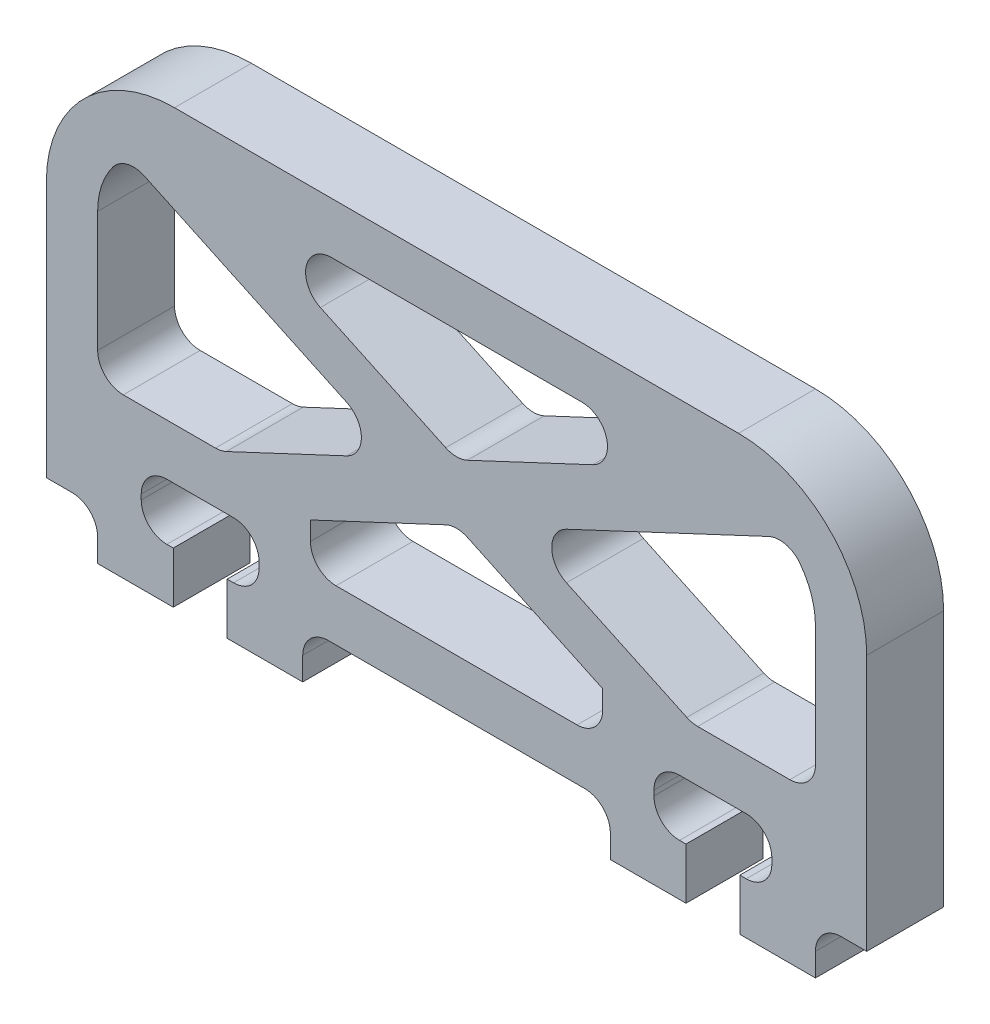
SolidWorks part; units mm, degrees
ref_plane "Front Plane" through (0, 0, 0) normal (0, 0, 1) x (1, 0, 0)
ref_plane "Top Plane" through (0, 0, 0) normal (0, 1, 0) x (1, 0, 0)
ref_plane "Right Plane" through (0, 0, 0) normal (1, 0, 0) x (0, 0, -1)
sketch "Sketch1" plane through (0, 0, 0) normal (0, 0, 1) x (1, 0, 0)
  line L0 (-10, -9.4) -> (-10, 7.5) construction
  line L1 (-16, 7.5) -> (16, 7.5)
  line L2 (-16, 7.5) -> (-16, -7.5)
  line L3 (-16, -7.5) -> (16, -7.5)
  line L4 (16, 7.5) -> (16, -7.5)
  line L5 (-16, 7.5) -> (16, -7.5) construction
  line L6 (-16, -7.5) -> (16, 7.5) construction
  line L7 (-16, -7.5) -> (-6, -7.5)
  line L9 (-14, -9.4) -> (-6, -9.4)
  line L10 (-6, -7.5) -> (-6, -9.4)
  line L11 (0, 7.5) -> (0, -7.5) construction
  line L12 (-11.05, -7.4) -> (-8.95, -7.4)
  line L13 (-11.05, -7.4) -> (-11.05, -9.4)
  line L14 (-11.05, -9.4) -> (-8.95, -9.4)
  line L15 (-8.95, -7.4) -> (-8.95, -9.4)
  line L16 (-11.05, -7.4) -> (-8.95, -9.4) construction
  line L17 (-11.05, -9.4) -> (-8.95, -7.4) construction
  line L18 (-12.3, -5.2) -> (-7.7, -5.2)
  line L19 (-12.3, -5.2) -> (-12.3, -7.4)
  line L20 (-12.3, -7.4) -> (-7.7, -7.4)
  line L21 (-7.7, -5.2) -> (-7.7, -7.4)
  line L22 (-12.3, -5.2) -> (-7.7, -7.4) construction
  line L23 (-12.3, -7.4) -> (-7.7, -5.2) construction
  line L24 (12.3, -5.2) -> (7.7, -5.2)
  line L25 (12.3, -5.2) -> (12.3, -7.4)
  line L26 (12.3, -7.4) -> (7.7, -7.4)
  line L27 (7.7, -5.2) -> (7.7, -7.4)
  line L28 (11.05, -7.4) -> (8.95, -7.4)
  line L29 (11.05, -7.4) -> (11.05, -9.4)
  line L30 (11.05, -9.4) -> (8.95, -9.4)
  line L31 (8.95, -7.4) -> (8.95, -9.4)
  line L32 (16, -7.5) -> (6, -7.5)
  line L33 (6, -7.5) -> (6, -9.4)
  line L34 (14, -9.4) -> (6, -9.4)
  line L36 (-14, -9.4) -> (-14, -7.5)
  line L37 (14, -9.4) -> (14, -7.5)
  point P0 (0, 0)
  point P11 (-10, -8.4)
  point P16 (-10, -6.3)
  dimension "D1" = 32
  dimension "D2" = 15
  dimension "D3" = 1.9
  dimension "D4" = 8
  dimension "D5" = 2.1
  dimension "D6" = 2
  dimension "D7" = 2.2
  dimension "D8" = 4.6
  dimension "D9" = 2
extrude "Boss-Extrude2" add sketch "Sketch1" along normal blind 3 contours L31 L26 L27 L24 L25 L29 L3 L4 L1 L2 L13 L20 L19 L18 L21 L15 | L3 L15 L9 L10 | L13 L3 L9 | L34 L31 L3 L33 | L3 L29 L34 region at (0, 0.2844, 0) region at (-12.525, -8.45, 0) region at (12.525, -8.45, 0) region at (-7.475, -8.45, 0) region at (7.475, -8.45, 0)
fillet "Fillet1" radius 5 2 edges at (16, 7.5, 1.5) (-16, 7.5, 1.5)
sketch "Sketch2" plane through (0, 0, 3) normal (0, 0, 1) x (1, 0, 0)
  line L0 (-6, -7.5) -> (6, -7.5) construction
  line L1 (16, -7.5) -> (-16, -7.5)
  line L2 (16, -7.5) -> (16, 7.5)
  line L3 (16, 7.5) -> (-16, 7.5)
  line L4 (-16, -7.5) -> (-16, 7.5)
  line L5 (16, -7.5) -> (-16, 7.5) construction
  line L6 (16, 7.5) -> (-16, -7.5) construction
  line L8 (16.4244, -6.5945) -> (-15.5756, 8.4055)
  line L9 (15.5756, 8.4055) -> (-16.4244, -6.5945)
  line L10 (15.5756, -8.4055) -> (-16.4244, 6.5945)
  line L11 (16.4244, 6.5945) -> (-15.5756, -8.4055)
  line L36 (-16, 2.5) -> (-16, -7.5) construction
  line L60 (11, 5.5) -> (-11, 5.5)
  line L61 (14, -3.2) -> (14, 2.5)
  line L62 (-14, -3.2) -> (-5.7, -3.2)
  line L63 (-5.7, -3.2) -> (-5.7, -5.5)
  line L64 (-5.7, -5.5) -> (5.7, -5.5)
  line L65 (5.7, -5.5) -> (5.7, -3.2)
  line L66 (5.7, -3.2) -> (14, -3.2)
  line L67 (14, -3.2) -> (14, 2.5)
  line L68 (11, 5.5) -> (-11, 5.5)
  line L70 (-14, -3.2) -> (-5.7, -3.2)
  line L71 (-5.7, -3.2) -> (-5.7, -5.5)
  line L72 (-5.7, -5.5) -> (5.7, -5.5)
  line L73 (5.7, -5.5) -> (5.7, -3.2)
  line L74 (5.7, -3.2) -> (14, -3.2)
  line L80 (-14, 2.5) -> (-14, -3.2)
  line L81 (-14, 2.5) -> (-14, -3.2)
  arc A4 (14, 2.5) -> (11, 5.5) centre (11, 2.5) ccw
  arc A5 (14, 2.5) -> (11, 5.5) centre (11, 2.5) ccw
  arc A8 (-11, 5.5) -> (-14, 2.5) centre (-11, 2.5) ccw
  arc A9 (-11, 5.5) -> (-14, 2.5) centre (-11, 2.5) ccw
  point P0 (0, 0)
  dimension "D1" = 1
  dimension "D2" = 1
  dimension "D3" = 2
extrude "Cut-Extrude1" cut sketch "Sketch2" against normal up to next contours L10 L70 L9 | L9 L68 L8 | L11 L8 L74 | L72 L73 L10 L11 L71 region at (0, -3.873, 3) region at (9.827, 0.2821, 3) region at (-9.827, 0.2821, 3) region at (0, 4.0348, 3)
fillet "Fillet2" radius 1 14 edges at (5.7, -5.5, 1.5) (-5.7, -5.5, 1.5) (0, -1.1044, 1.5) (9.1827, -3.2, 1.5) (2.3561, 0, 1.5) (9.3773, 5.5, 1.5) (-9.3773, 5.5, 1.5) (0, 1.1044, 1.5) (-2.3561, 0, 1.5) (-9.1827, -3.2, 1.5) (14, -3.2, 1.5) (12.8036, 4.8973, 1.5) (-12.8036, 4.8973, 1.5) (-14, -3.2, 1.5)
fillet "Fillet3" radius 1 12 edges at (12.3, -7.4, 1.5) (12.3, -5.2, 1.5) (7.7, -5.2, 1.5) (7.7, -7.4, 1.5) (-12.3, -7.4, 1.5) (-7.7, -7.4, 1.5) (-7.7, -5.2, 1.5) (-12.3, -5.2, 1.5) (14, -7.5, 1.5) (6, -7.5, 1.5) (-14, -7.5, 1.5) (-6, -7.5, 1.5)
